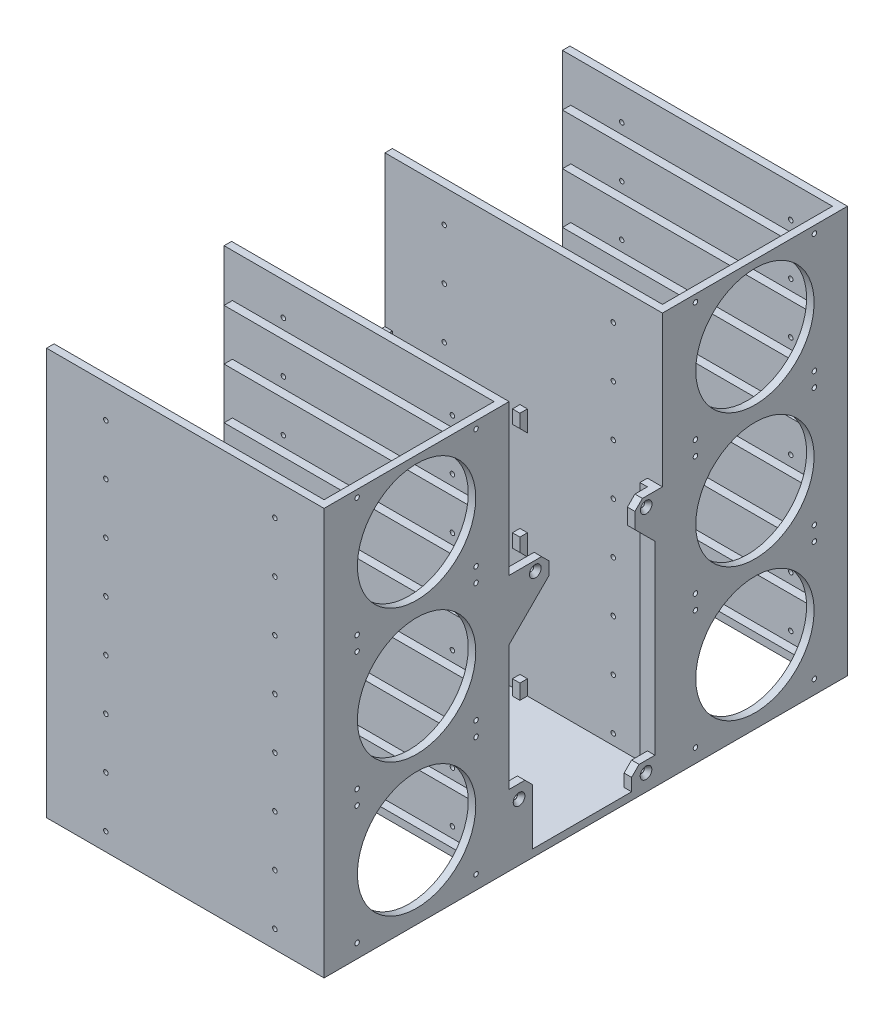
SolidWorks part; units mm, degrees
ref_plane "Front Plane" through (0, 0, 0) normal (0, 0, 1) x (1, 0, 0)
ref_plane "Top Plane" through (0, 0, 0) normal (0, 1, 0) x (1, 0, 0)
ref_plane "Right Plane" through (0, 0, 0) normal (1, 0, 0) x (0, 0, -1)
sketch "Sketch1" plane through (0, 0, 0) normal (0, 1, 0) x (1, 0, 0)
  line L1 (-83.25, 55.5) -> (83.25, 55.5)
  line L2 (-83.25, 55.5) -> (-83.25, -55.5)
  line L3 (-83.25, -55.5) -> (83.25, -55.5)
  line L4 (83.25, 55.5) -> (83.25, -55.5)
  line L5 (-83.25, 55.5) -> (83.25, -55.5) construction
  line L6 (-83.25, -55.5) -> (83.25, 55.5) construction
  point P0 (0, 0)
  dimension "D1" = 166.5
  dimension "D2" = 111
extrude "Boss-Extrude1" add sketch "Sketch1" along normal blind 30.5
shell "Shell1" thickness 4.5 removed face at (-83.25, 15.25, 0) removed face at (0, 30.5, 0)
sketch "Sketch2" plane through (0, 4.5, 0) normal (0, 1, 0) x (1, 0, 0)
  line L5 (78.75, 51) -> (-83.25, 51) construction
  line L6 (-78.25, 46) -> (78.75, 46)
  line L9 (-78.25, 46) -> (-78.25, -46)
  line L10 (-78.25, -46) -> (78.75, -46)
  line L11 (78.75, 46) -> (78.75, -46)
  line L12 (-83.25, -51) -> (78.75, -51) construction
  line L13 (-83.25, 51) -> (-83.25, -51) construction
  line L14 (78.75, -51) -> (78.75, 51) construction
  point P0 (0, 0)
  dimension "D1" = 5
  dimension "D2" = 5
  dimension "D3" = 5
extrude "Cut-Extrude1" cut sketch "Sketch2" against normal up to next
hole_wizard "Tap Drill for #6-32 Tap1" positions "Sketch4" profile "Sketch5" hole size "#6-32" standard "ANSI Inch" end condition up to next
sketch "Sketch4" plane through (0, 0, -55.5) normal (0, 0, -1) x (-1, 0, 0)
  line L0 (-78.75, 4.5) -> (83.25, 4.5) construction
  line L2 (-78.75, 30.5) -> (-78.75, 4.5) construction
  point P0 (47.66, 10.84)
  point P2 (-53.75, 10.84)
  dimension "D1" = 6.34
  dimension "D2" = 25
  dimension "D3" = 101.41
sketch "Sketch5" plane through (-47.66, 10.84, -55.5) normal (1, 0, 0) x (0, 1, 0)
  line L0 (0, 0) -> (0, 4.5)
  line L1 (0, 4.5) -> (1.3525, 4.5)
  line L2 (1.3525, 4.5) -> (1.3525, 0)
  line L5 (1.3525, 0) -> (0, 0)
  line L11 (0, -6.35) -> (0, 107.95) construction
  dimension "Thru Hole Dia." = 2.7051
  dimension "Thru Hole Depth" = 4.5
mirror "Mirror1" about plane through (0, 0, 0) normal (0, 0, 1) of "Tap Drill for #6-32 Tap1"
pattern_linear "LPattern1" count 8 spacing 30.5 along (0, 1, 0) of bodies 104
combine bodies "Combine1" operation type add bodies to combine 104 105
sketch "Sketch7" plane through (-83.25, 0, 0) normal (-1, 0, 0) x (0, 0, 1)
  line L1 (-51, 30.5) -> (51, 30.5)
  line L2 (-51, 30.5) -> (-51, 35)
  line L3 (-51, 35) -> (51, 35)
  line L4 (51, 30.5) -> (51, 35)
extrude "Cut-Extrude2" cut sketch "Sketch7" against normal up to surface (5 mm away) up to face at (-78.25, 32.75, 0)
combine bodies "Combine2" operation type add bodies to combine 109 110 112 111 114 108 113
sketch "Sketch8" plane through (-83.25, 0, 0) normal (-1, 0, 0) x (0, 0, 1)
  line L1 (-51, 61) -> (51, 61)
  line L2 (-51, 61) -> (-51, 218)
  line L3 (-51, 218) -> (51, 218)
  line L4 (51, 61) -> (51, 218)
extrude "Cut-Extrude3" cut sketch "Sketch8" against normal up to surface (5 mm away) up to face at (-78.25, 215.75, 0)
sketch "Sketch9" plane through (83.25, 0, 0) normal (1, 0, 0) x (0, 0, -1)
  line L0 (-55.5, 244) -> (55.5, 244) construction
  line L1 (-40, 244) -> (40, 244) construction
  line L2 (-40, 244) -> (-40, 4) construction
  line L3 (-40, 4) -> (40, 4) construction
  line L4 (40, 244) -> (40, 4) construction
  line L5 (0, 244) -> (0, 4) construction
  line L6 (-40, 164) -> (40, 164) construction
  line L7 (-40, 84) -> (40, 84) construction
  circle A0 centre (0, 204) radius 35.5
  circle A1 centre (0, 124) radius 35.5
  circle A2 centre (0, 44) radius 35.5
  dimension "D5" = 71
  dimension "D7" = 71
  dimension "D8" = 71
  dimension "D1" = 240
  dimension "D2" = 80
  dimension "D3" = 80
  dimension "D4" = 80
  dimension "D6" = 40
  dimension "D9" = 40
extrude "Cut-Extrude4" cut sketch "Sketch9" against normal up to next
sketch "Fan Dimensions" plane through (83.25, 0, 0) normal (1, 0, 0) x (0, 0, -1)
  line L0 (0, 239.5) -> (0, 168.5) construction
  line L1 (-40, 204) -> (40, 204) construction
  line L2 (-40, 244) -> (40, 244) construction
  line L3 (-40, 244) -> (-40, 164) construction
  line L4 (-40, 164) -> (40, 164) construction
  line L5 (40, 244) -> (40, 164) construction
  line L6 (-40, 244) -> (40, 164) construction
  line L7 (-40, 164) -> (40, 244) construction
  circle A0 centre (0, 204) radius 35.5 construction
  circle A1 centre (-35.675, 239.675) radius 2.175
  circle A2 centre (35.675, 239.675) radius 2.175
  circle A3 centre (35.675, 168.325) radius 2.175
  circle A4 centre (-35.675, 168.325) radius 2.175
  point P5 (0, 204)
  dimension "D2" = 80
  dimension "D3" = 4.35
  dimension "D1" = 80
  dimension "D4" = 4.325
hole_wizard "Tap Drill for #6-32 Tap2" positions "Sketch11" profile "Sketch12" hole size "#6-32" standard "ANSI Inch" end condition up to next
sketch "Sketch11" plane through (83.25, 0, 0) normal (1, 0, 0) x (0, 0, -1)
  point P0 (-35.675, 239.675)
  point P3 (35.675, 239.675)
  point P6 (35.675, 168.325)
  point P9 (-35.675, 168.325)
sketch "Sketch12" plane through (83.25, 239.675, 35.675) normal (0, 1, 0) x (0, 0, -1)
  line L0 (0, 0) -> (0, 4.5)
  line L1 (0, 4.5) -> (1.3525, 4.5)
  line L2 (1.3525, 4.5) -> (1.3525, 0)
  line L5 (1.3525, 0) -> (0, 0)
  line L11 (0, -6.35) -> (0, 107.95) construction
  dimension "Thru Hole Dia." = 2.7051
  dimension "Thru Hole Depth" = 4.5
ref_plane "Plane1" through (0, 164, 0) normal (0, 1, 0) x (1, 0, 0)
mirror "Mirror2" about plane through (0, 164, 0) normal (0, 1, 0) of "Tap Drill for #6-32 Tap2"
ref_plane "Plane2" through (0, 124, 0) normal (0, 1, 0) x (1, 0, 0)
mirror "Mirror3" about plane through (0, 124, 0) normal (0, 1, 0) of "Tap Drill for #6-32 Tap2"
sketch "Sketch13" plane through (0, 0, 0) normal (0, -1, 0) x (1, 0, 0)
  line L0 (83.25, 55.5) -> (83.25, -55.5) construction
  line L1 (-83.25, -55.5) -> (83.25, -55.5)
  line L2 (-83.25, -55.5) -> (-83.25, -147.5)
  line L3 (-83.25, -147.5) -> (83.25, -147.5)
  line L4 (83.25, -55.5) -> (83.25, -147.5)
  dimension "D1" = 92
extrude "Boss-Extrude2" add sketch "Sketch13" against normal blind 4.5
ref_plane "Plane3" through (0, 0, -101.5) normal (0, 0, -1) x (-1, 0, 0)
mirror "Mirror4" about plane through (0, 0, -101.5) normal (0, 0, -1) of bodies 122 125
sketch "Sketch17" plane through (-78.25, 0, 0) normal (-1, 0, 0) x (0, 0, 1)
  line L0 (-46, 35) -> (-51, 30.5)
  line L1 (-51, 30.5) -> (-46, 30.5)
  line L2 (-46, 30.5) -> (-46, 35)
  line L3 (-51, 61) -> (-46, 65.5)
  line L4 (-46, 65.5) -> (-46, 61)
  line L5 (-46, 61) -> (-51, 61)
  line L6 (-51, 91.5) -> (-46, 96)
  line L7 (-46, 96) -> (-46, 91.5)
  line L8 (-46, 91.5) -> (-51, 91.5)
  line L9 (-51, 122) -> (-46, 126.5)
  line L10 (-46, 126.5) -> (-46, 122)
  line L11 (-46, 122) -> (-51, 122)
  line L12 (-51, 152.5) -> (-46, 157)
  line L13 (-46, 157) -> (-46, 152.5)
  line L14 (-46, 152.5) -> (-51, 152.5)
  line L15 (-51, 183) -> (-46, 187.5)
  line L16 (-46, 187.5) -> (-46, 183)
  line L17 (-46, 183) -> (-51, 183)
  line L18 (-51, 213.5) -> (-46, 218)
  line L19 (-46, 218) -> (-46, 213.5)
  line L20 (-46, 213.5) -> (-51, 213.5)
extrude "Cut-Extrude7" cut sketch "Sketch17" against normal up to surface (157 mm away)
mirror "Mirror5" about plane through (0, 0, 0) normal (0, 0, 1) of "Cut-Extrude7"
mirror "Mirror6" about plane through (0, 0, -101.5) normal (0, 0, -1) of "Mirror5"
sketch "Sketch31" plane through (0, 4.5, 0) normal (0, 1, 0) x (1, 0, 0)
  line L1 (-83.25, 254) -> (-78.25, 254)
  line L2 (-83.25, 254) -> (-83.25, 152)
  line L3 (-83.25, 152) -> (-78.25, 152)
  line L4 (-78.25, 254) -> (-78.25, 152)
  line L5 (-83.25, 51) -> (-78.25, 51)
  line L6 (-83.25, 51) -> (-83.25, -51)
  line L7 (-83.25, -51) -> (-78.25, -51)
  line L8 (-78.25, 51) -> (-78.25, -51)
extrude "Cut-Extrude11" cut sketch "Sketch31" against normal up to next
sketch "Sketch33" plane through (83.25, 0, 0) normal (1, 0, 0) x (0, 0, -1)
  line L1 (147.5, 4.5) -> (143, 4.5)
  line L2 (147.5, 4.5) -> (147.5, 153.7)
  line L3 (147.5, 153.7) -> (143, 153.7)
  line L4 (143, 4.5) -> (143, 153.7)
  dimension "D1" = 4.5
  dimension "D2" = 149.2
extrude "Boss-Extrude3" add sketch "Sketch33" against normal blind 4.5
pattern_linear "LPattern2" count 3 spacing 81 along (-1, 0, 0) of "Boss-Extrude3"
sketch "Sketch34" plane through (-83.25, 0, 0) normal (-1, 0, 0) x (0, 0, 1)
  line L0 (-147.5, 153.7) -> (-147.5, 0) construction
  line L1 (-152, 0) -> (-51, 0) construction
  line L2 (-143, 25) -> (-147.5, 25)
  line L3 (-143, 153.7) -> (-143, 4.5) construction
  line L4 (-147.5, 25) -> (-147.5, 76.85)
  line L5 (-147.5, 76.85) -> (-143, 81.35)
  line L6 (-143, 81.35) -> (-143, 25)
  line L7 (-143, 89.35) -> (-147.5, 89.35)
  line L8 (-147.5, 89.35) -> (-147.5, 141.2)
  line L9 (-147.5, 141.2) -> (-143, 145.7)
  line L10 (-143, 145.7) -> (-143, 89.35)
  line L11 (-147.5, 153.7) -> (-143, 153.7) construction
  line L12 (-55.5, 4.5) -> (-143, 4.5) construction
  line L13 (-147.5, 25) -> (-143, 25)
  line L14 (-147.5, 25) -> (-147.5, 13.5)
  line L15 (-147.5, 13.5) -> (-143, 13.5)
  line L16 (-143, 25) -> (-143, 13.5)
  line M20 (-143, 4.5) -> (-143, 153.7)
  dimension "D1" = 45
  dimension "D2" = 45
  dimension "D3" = 8
  dimension "D4" = 8
  dimension "D5" = 9
extrude "Cut-Extrude12" cut sketch "Sketch34" against normal up to surface (85.5 mm away) contours L5 L4 L2 M20 | L14 L15 L2 M20 | L10 L7 L8 L9 region at (-83.25, 19.25, -145.25) region at (-83.25, 52.0656, -145.2188) up to face at (2.25, 79.1, -145.25)
sketch "Sketch35" plane through (78.75, 0, 0) normal (-1, 0, 0) x (0, 0, 1)
  line L4 (-147.5, 153.7) -> (-147.5, 4.5)
  line L5 (-147.5, 4.5) -> (-143, 4.5)
  line L6 (-143, 4.5) -> (-143, 153.7)
  line L7 (-143, 153.7) -> (-147.5, 153.7)
  line L8 (-147.5, 153.7) -> (-147.5, 4.5)
  line L9 (-147.5, 4.5) -> (-143, 4.5)
  line L10 (-143, 4.5) -> (-143, 153.7)
  line L11 (-143, 153.7) -> (-147.5, 153.7)
  dimension "D1" = 0
extrude "Boss-Extrude4" add sketch "Sketch35" along normal blind 4.5
sketch "Sketch36" plane through (83.25, 0, 0) normal (1, 0, 0) x (0, 0, -1)
  line L0 (147.5, 153.7) -> (55.5, 153.7) construction
  line L1 (55.5, 4.5) -> (69.5, 4.5)
  line L2 (55.5, 4.5) -> (55.5, 42.5)
  line L3 (55.5, 42.5) -> (69.5, 42.5)
  line L4 (69.5, 4.5) -> (69.5, 42.5)
  line L5 (55.5, 244) -> (55.5, 4.5) construction
  line L7 (55.5, 153.7) -> (79.5, 153.7)
  line L8 (55.5, 153.7) -> (55.5, 141.7)
  line L9 (55.5, 141.7) -> (79.5, 141.7)
  line L10 (79.5, 153.7) -> (79.5, 141.7)
  line L11 (143, 153.7) -> (131, 153.7)
  line L12 (143, 153.7) -> (143, 139.7)
  line L13 (143, 139.7) -> (131, 139.7)
  line L14 (131, 153.7) -> (131, 139.7)
  line L15 (143, 4.5) -> (129, 4.5)
  line L16 (143, 4.5) -> (143, 16.5)
  line L17 (143, 16.5) -> (129, 16.5)
  line L18 (129, 4.5) -> (129, 16.5)
  dimension "D1" = 14
  dimension "D2" = 38
  dimension "D3" = 24
  dimension "D4" = 12
  dimension "D5" = 12
  dimension "D6" = 14
  dimension "D7" = 14
  dimension "D8" = 12
extrude "Boss-Extrude5" add sketch "Sketch36" against normal blind 4.5
sketch "Sketch37" plane through (83.25, 0, 0) normal (1, 0, 0) x (0, 0, -1)
  line L0 (55.5, 244) -> (55.5, 153.7) construction
  line L1 (79.5, 153.7) -> (55.5, 153.7) construction
  line L2 (143, 139.7) -> (143, 16.5) construction
  line L3 (55.5, 141.7) -> (55.5, 42.5) construction
  line L4 (129, 4.5) -> (69.5, 4.5) construction
  circle A0 centre (71.225, 148.015) radius 1.355
  circle A1 centre (137.775, 148.015) radius 1.355
  circle A2 centre (61.475, 34.415) radius 1.355
  circle A3 centre (137.645, 10.055) radius 1.355
  dimension "D1" = 2.71
  dimension "D4" = 2.71
  dimension "D6" = 2.71
  dimension "D9" = 2.71
  dimension "D2" = 15.725
  dimension "D3" = 5.685
  dimension "D5" = 5.225
  dimension "D7" = 5.975
  dimension "D8" = 29.915
  dimension "D10" = 5.555
  dimension "D11" = 5.355
extrude "Cut-Extrude13" cut sketch "Sketch37" against normal up to next
sketch "Sketch38" plane through (83.25, 0, 0) normal (1, 0, 0) x (0, 0, -1)
  line L0 (79.5, 141.7) -> (55.5, 117.7)
  line L1 (55.5, 141.7) -> (55.5, 42.5) construction
  line L2 (55.5, 117.7) -> (55.5, 141.7)
  line L3 (55.5, 141.7) -> (79.5, 141.7)
  line L4 (131, 139.7) -> (143, 127.7)
  line L5 (143, 139.7) -> (143, 16.5) construction
  line L6 (143, 127.7) -> (143, 139.7)
  line L7 (143, 139.7) -> (131, 139.7)
  dimension "D1" = 45
  dimension "D2" = 45
extrude "Boss-Extrude6" add sketch "Sketch38" along normal up to surface (-4.5 mm away) up to face at (78.75, 148.015, -72.58)
sketch "Sketch39" plane through (83.25, 0, 0) normal (1, 0, 0) x (0, 0, -1)
  circle A0 centre (71.225, 148.015) radius 3.5
  circle A1 centre (137.775, 148.015) radius 3.5
  circle A2 centre (137.645, 10.055) radius 3.5
  circle A3 centre (61.475, 34.415) radius 3.5
  dimension "D1" = 7
  dimension "D2" = 7
  dimension "D3" = 7
  dimension "D4" = 7
extrude "Cut-Extrude14" cut sketch "Sketch39" against normal blind 2.5 draft 39
chamfer "Chamfer1" distance 4.5 angle 45 4 edges at (81, 16.5, -129) (81, 153.7, -131) (81, 153.7, -79.5) (81, 42.5, -69.5)
equation "\"Drive Lenght\"= 162"
equation "\"Drive Width\"= 102"
equation "\"Drive Thickness\"= 25.5"
equation "\"D1@Sketch1\"=\"Drive Lenght\"+\"Spacer\""
equation "\"D2@Sketch1\"=\"Drive Width\" +\"Spacer\"*2"
equation "\"D1@Boss-Extrude1\"=\"Drive Thickness\"+5"
equation "\"D1@Sketch2\"=5"
equation "\"D2@Sketch2\"=5"
equation "\"D3@Sketch2\"=5"
equation "\"Spacer\"= 4.5"
equation "\"Drive Hole from botton\"= 6.34"
equation "\"Between Drive holes\"= 101.41"
equation "\"Drive hole to fron\" = 25"
equation "\"D1@Sketch4\"=\"Drive Hole from botton\""
equation "\"D2@Sketch4\"= \"Drive hole to fron\""
equation "\"D3@Sketch4\"=\"Between Drive holes\""
equation "\"D3@LPattern1\"=\"Drive Thickness\"+5 "
equation "\"D6@Sketch9\"=40"
equation "\"D7@Sketch9\"=\"D5@Sketch9\""
equation "\"D8@Sketch9\"=\"D5@Sketch9\""
equation "\"D2@Fan Dimensions\" = \"D1@Fan Dimensions\""
equation "\"Power Supply Thickness\"= 87.5"
equation "\"D1@Boss-Extrude2\"=\"Spacer\""
equation "\"D1@Sketch13\"= \"Power Supply Thickness\" + \"Spacer\""
equation "\"Power Supply Height\"= 149.2"
equation "\"Mount Hole Diameter\"= 2.71"
equation "\"D1@Sketch33\"=\"Spacer\""
equation "\"D2@Sketch33\"=\"Power Supply Height\""
equation "\"D1@Boss-Extrude3\"=\"Spacer\""
equation "\"D3@LPattern2\"=\"Drive Lenght\"/2"
equation "\"D1@Boss-Extrude5\"=\"Spacer\""
equation "\"D1@Sketch37\"=\"Mount Hole Diameter\""
equation "\"D2@Sketch37\"=14.37 + \"Mount Hole Diameter\"/2"
equation "\"D3@Sketch37\"=4.33 + \"Mount Hole Diameter\"/2"
equation "\"D4@Sketch37\"=\"Mount Hole Diameter\""
equation "\"D5@Sketch37\"=3.87 +\"Mount Hole Diameter\"/2"
equation "\"D6@Sketch37\"=\"Mount Hole Diameter\""
equation "\"D7@Sketch37\"=4.62 +\"Mount Hole Diameter\"/2"
equation "\"D8@Sketch37\"=28.56 +\"Mount Hole Diameter\"/2"
equation "\"D9@Sketch37\"=\"Mount Hole Diameter\""
equation "\"D10@Sketch37\"=4.2 +\"Mount Hole Diameter\"/2"
equation "\"D2@Sketch39\"=\"D1@Sketch39\""
equation "\"D3@Sketch39\"=\"D1@Sketch39\""
equation "\"D4@Sketch39\"=\"D3@Sketch39\""
equation "\"Counter Sink Depth\"= 2.5"
equation "\"D1@Cut-Extrude14\"=\"Counter Sink Depth\""
equation "\"D11@Sketch37\"=4 +\"Mount Hole Diameter\"/2"
equation "\"D1@Chamfer1\"=\"Spacer\""
